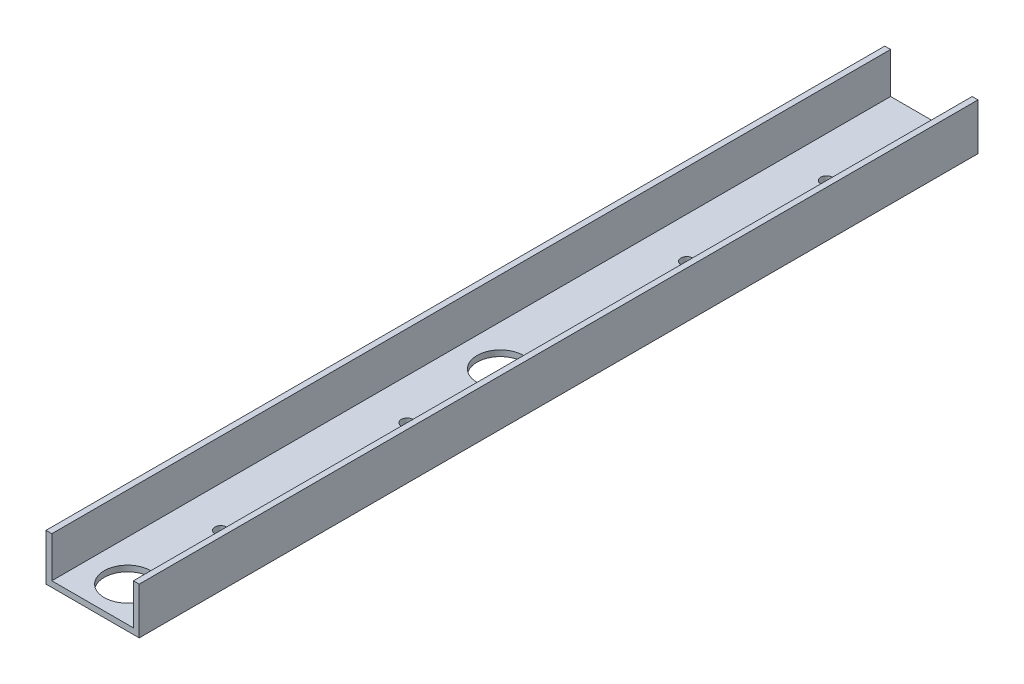
SolidWorks part; units mm, degrees
ref_plane "Front" through (0, 0, 0) normal (0, 0, 1) x (1, 0, 0)
ref_plane "Top" through (0, 0, 0) normal (0, 1, 0) x (1, 0, 0)
ref_plane "Right" through (0, 0, 0) normal (1, 0, 0) x (0, 0, -1)
sketch "Sketch1" plane through (0, 0, 0) normal (0, 0, 1) x (1, 0, 0)
  line L0 (47.625, 3.175) -> (47.625, 25.4)
  line L1 (0, 0) -> (50.8, 0)
  line L2 (0, 0) -> (0, 25.4)
  line L4 (50.8, 0) -> (50.8, 25.4)
  line L5 (3.175, 3.175) -> (47.625, 3.175)
  line L6 (3.175, 3.175) -> (3.175, 25.4)
  line L7 (50.8, 25.4) -> (47.625, 25.4)
  line L8 (0, 25.4) -> (3.175, 25.4)
  dimension "D1" = 25.4
  dimension "D2" = 50.8
  dimension "D3" = 3.175
extrude "Boss-Extrude1" add sketch "Sketch1" along normal blind 457.2
sketch "Sketch2" plane through (0, 3.175, 0) normal (0, 1, 0) x (1, 0, 0)
  line L0 (47.625, -457.2) -> (3.175, -457.2) construction
  circle A0 centre (25.4, -438.15) radius 12.7
  circle A1 centre (25.4, -234.95) radius 12.7
  circle A2 centre (25.4, -387.35) radius 3.175
  circle A3 centre (25.4, -285.75) radius 3.175
  point P10 (25.4, -361.0472)
  dimension "D1" = 25.4
  dimension "D2" = 19.05
  dimension "D3" = 203.2
  dimension "D4" = 6.35
  dimension "D5" = 50.8
  dimension "D6" = 50.8
extrude "Cut-Extrude1" cut sketch "Sketch2" against normal up to next
sketch "Sketch3" plane through (0, 3.175, 0) normal (0, 1, 0) x (1, 0, 0)
  circle A0 centre (25.4, -133.35) radius 3.175
  circle A1 centre (25.4, -57.15) radius 3.175
  circle A2 centre (25.4, -234.95) radius 12.7 construction
  point P4 (27.6321, -213.4242)
  point P5 (26.7701, -178.6687)
  point P6 (21.3514, -135.6914)
  point P7 (0, 0)
  point P8 (25.4, -192.0388)
  point P9 (25.4, -141.7417)
  point P12 (23.7333, -231.9219)
  dimension "D1" = 6.35
  dimension "D2" = 76.2
  dimension "D3" = 101.6
extrude "Cut-Extrude2" cut sketch "Sketch3" against normal up to next
